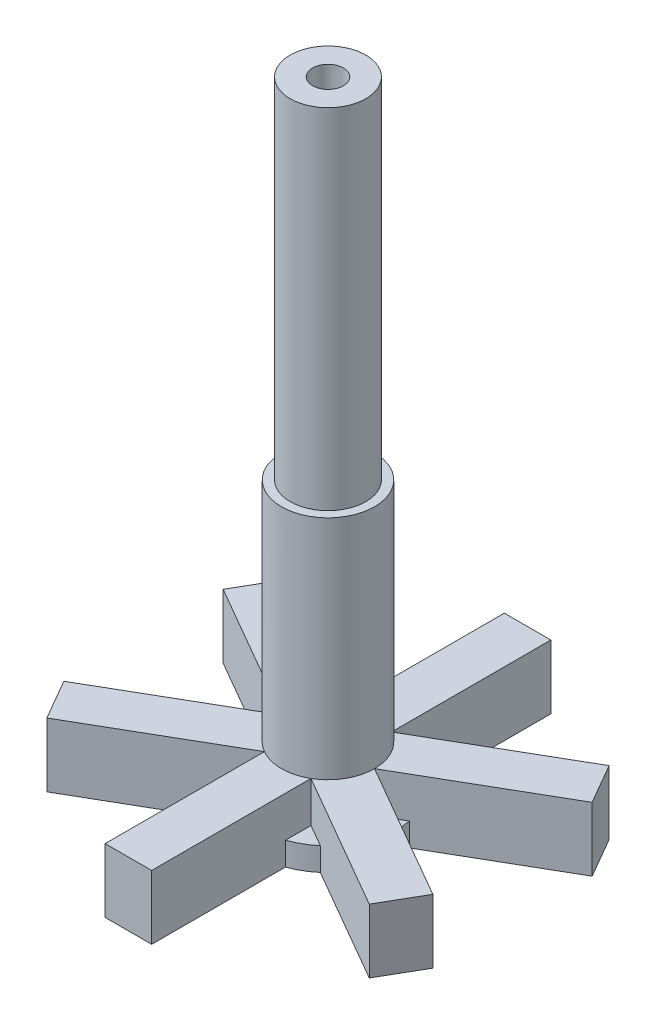
SolidWorks part; units mm, degrees
ref_plane "Front Plane" through (0, 0, 0) normal (0, 0, 1) x (1, 0, 0)
ref_plane "Top Plane" through (0, 0, 0) normal (0, 1, 0) x (1, 0, 0)
ref_plane "Right Plane" through (0, 0, 0) normal (1, 0, 0) x (0, 0, -1)
sketch "Sketch1" plane through (0, 0, 0) normal (0, 1, 0) x (1, 0, 0)
  line L48 (-2, -5.6569) -> (2, -5.6569)
  line L55 (2, -5.6569) -> (2, -17.1569)
  line L62 (2, -17.1569) -> (-2, -17.1569)
  line L69 (-2, -17.1569) -> (-2, -5.6569)
  line L70 (-15.8583, -6.8464) -> (-5.899, -1.0964)
  line L71 (-5.899, -1.0964) -> (-3.899, -4.5605)
  line L72 (-3.899, -4.5605) -> (-13.8583, -10.3105)
  line L73 (-13.8583, -10.3105) -> (-15.8583, -6.8464)
  line L74 (-13.8583, 10.3105) -> (-3.899, 4.5605)
  line L75 (-3.899, 4.5605) -> (-5.899, 1.0964)
  line L76 (-5.899, 1.0964) -> (-15.8583, 6.8464)
  line L77 (-15.8583, 6.8464) -> (-13.8583, 10.3105)
  line L78 (2, 17.1569) -> (2, 5.6569)
  line L79 (2, 5.6569) -> (-2, 5.6569)
  line L80 (-2, 5.6569) -> (-2, 17.1569)
  line L81 (-2, 17.1569) -> (2, 17.1569)
  line L82 (15.8583, 6.8464) -> (5.899, 1.0964)
  line L83 (5.899, 1.0964) -> (3.899, 4.5605)
  line L84 (3.899, 4.5605) -> (13.8583, 10.3105)
  line L85 (13.8583, 10.3105) -> (15.8583, 6.8464)
  line L86 (13.8583, -10.3105) -> (3.899, -4.5605)
  line L87 (3.899, -4.5605) -> (5.899, -1.0964)
  line L88 (5.899, -1.0964) -> (15.8583, -6.8464)
  line L89 (15.8583, -6.8464) -> (13.8583, -10.3105)
  line L90 (-2, 5.6569) -> (-2, 3.4641)
  line L91 (2, 5.6569) -> (2, 3.4641)
  line L92 (3.899, 4.5605) -> (2, 3.4641)
  line L93 (5.899, 1.0964) -> (4, 0)
  line L94 (5.899, -1.0964) -> (4, 0)
  line L95 (3.899, -4.5605) -> (2, -3.4641)
  line L96 (2, -5.6569) -> (2, -3.4641)
  line L97 (-2, -5.6569) -> (-2, -3.4641)
  line L98 (-3.899, -4.5605) -> (-2, -3.4641)
  line L99 (-5.899, -1.0964) -> (-4, 0)
  line L100 (-5.899, 1.0964) -> (-4, 0)
  line L101 (-3.899, 4.5605) -> (-2, 3.4641)
  circle A2 centre (0, 0) radius 4
  arc A3 (2, -5.6569) -> (3.899, -4.5605) centre (0, 0) ccw
  arc A4 (-3.899, -4.5605) -> (-2, -5.6569) centre (0, 0) ccw
  arc A5 (-5.899, 1.0964) -> (-5.899, -1.0964) centre (0, 0) ccw
  arc A6 (-2, 5.6569) -> (-3.899, 4.5605) centre (0, 0) ccw
  arc A7 (3.899, 4.5605) -> (2, 5.6569) centre (0, 0) ccw
  arc A8 (5.899, -1.0964) -> (5.899, 1.0964) centre (0, 0) ccw
  point P9 (0, -5.6569)
  point P31 (0, 0)
  point P32 (0, 0)
  point P33 (0, 0)
  point P46 (0.0289, 0.0554)
  dimension "D1" = 8
  dimension "D2" = 6
  dimension "D3" = 2
  dimension "D4" = 4
  dimension "D5" = 11.5
  dimension "D6" = 6
extrude "Boss-Extrude1" add sketch "Sketch1" along normal blind 25 contours A2
extrude "Boss-Extrude3" add sketch "Sketch1<4>" along normal blind 2 contours L90 A6 L101 | A2 L101 L75 L100 | L100 A5 L99 | A2 L99 L71 L98 | L98 A4 L97 | A2 L97 L48 L96 | L96 A3 L95 | A2 L95 L87 L94 | L94 A8 L93 | A2 L93 L83 L92 | L92 A7 L91 | A2 L91 L79 L90 region at (0, 0, 4.7348) region at (-2.6553, 0, 4.5992) region at (2.6553, 0, 4.5992) region at (-4.1005, 0, 2.3674) region at (4.1005, 0, 2.3674) region at (-5.3107, 0, 0) region at (-4.1005, 0, -2.3674) region at (4.1005, 0, -2.3674) region at (5.3107, 0, 0) region at (-2.6553, 0, -4.5992) region at (0, 0, -4.7348) region at (2.6553, 0, -4.5992)
sketch "Sketch1<4>" plane through (0, 0, 0) normal (0, 1, 0) x (1, 0, 0) same geometry as "Sketch1"
extrude "Boss-Extrude2" add sketch "Sketch1<3>" along normal blind 5.5 contours L62 | A2 L99 L71 L98 | A2 L95 L87 L94 | A2 L93 L83 L92 | A2 L91 L79 L90 | A2 L101 L75 L100 | A2 L97 L48 L96 | L69 L48 L55 L62 | L70 L71 L72 L73 | L74 L75 L76 L77 | L78 L79 L80 L81 | L82 L83 L84 L85 | L86 L87 L88 L89 region at (0, 0, 4.7348) region at (-4.1005, 0, 2.3674) region at (4.1005, 0, 2.3674) region at (-4.1005, 0, -2.3674) region at (4.1005, 0, -2.3674) region at (0, 0, -4.7348)
sketch "Sketch1<3>" plane through (0, 0, 0) normal (0, 1, 0) x (1, 0, 0) same geometry as "Sketch1"
sketch "Sketch2" plane through (0, 25, 0) normal (0, 1, 0) x (1, 0, 0)
  circle A1 centre (0, 0) radius 3.25
  circle A3 centre (0, 0) radius 1.25
  dimension "D1" = 2
  dimension "D2" = 2.5
extrude "Boss-Extrude6" add sketch "Sketch2" along normal blind 30 contours A1
sketch "Sketch3" plane through (0, 55, 0) normal (0, 1, 0) x (1, 0, 0)
  circle A0 centre (0, 0) radius 1.325
  dimension "D1" = 2.65
extrude "Cut-Extrude1" cut sketch "Sketch3" against normal blind 10
